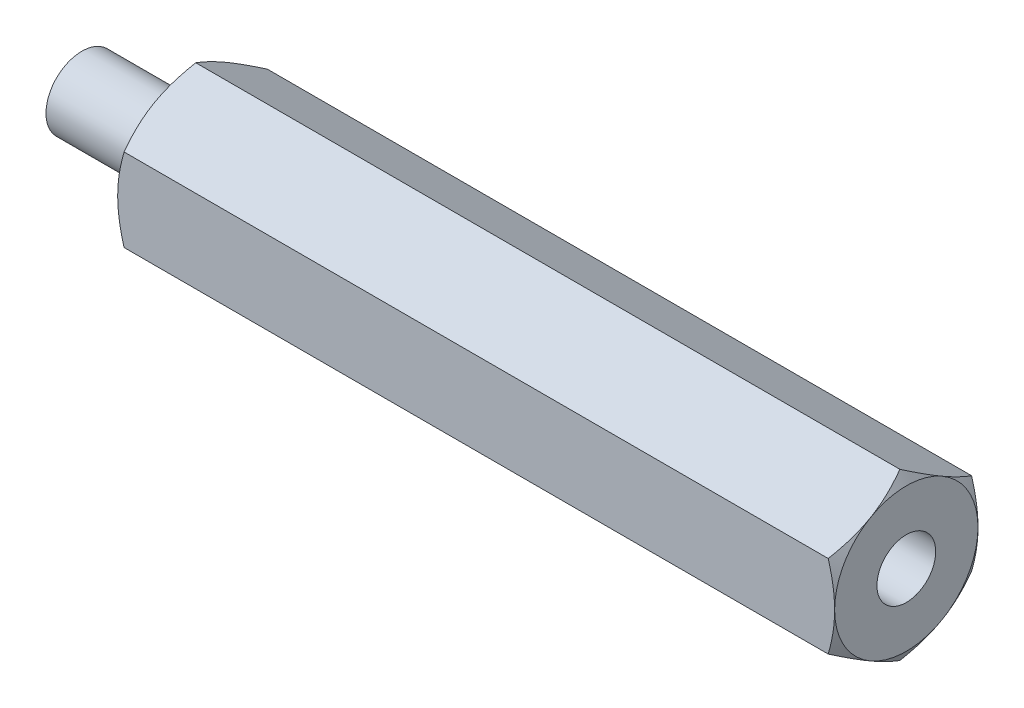
SolidWorks part; units mm, degrees
material "一般構造用鋼またはSUM材"
ref_plane "Front Plane" through (0, 0, 0) normal (0, 0, 1) x (1, 0, 0)
ref_plane "Top Plane" through (0, 0, 0) normal (0, 1, 0) x (1, 0, 0)
ref_plane "Right Plane" through (0, 0, 0) normal (1, 0, 0) x (0, 0, -1)
ref_axis "Axis_X" through (-88.99, 0, 0) along (1, 0, 0)
ref_axis "Axis_Y" through (0, 55, 0) along (0, -1, 0)
ref_axis "Axis_Z" through (0, 0, -88.99) along (0, 0, 1)
sketch "Sketch1" plane through (0, 0, 0) normal (1, 0, 0) x (0, 0, -1)
  line L1 (3, 1.7321) -> (0, 3.4641)
  line L2 (0, 3.4641) -> (-3, 1.7321)
  line L3 (-3, 1.7321) -> (-3, -1.7321)
  line L4 (-3, -1.7321) -> (0, -3.4641)
  line L5 (0, -3.4641) -> (3, -1.7321)
  line L6 (3, -1.7321) -> (3, 1.7321)
  circle A0 centre (0, 0) radius 3 construction
  dimension "B" = 6
extrude "Boss-Extrude1" add sketch "Sketch1" along normal blind 30
sketch "Sketch2" plane through (0, 0, 0) normal (0, 0, 1) x (1, 0, 0)
  line L0 (0, 3.4641) -> (0.2679, 3.4641)
  line L1 (0, 3.4641) -> (0, 3)
  line L2 (0.2679, 3.4641) -> (0, 3)
  line L3 (29.7321, 3.4641) -> (30, 3)
  line L4 (30, 3.4641) -> (30, 3)
  line L5 (30, 3.4641) -> (29.7321, 3.4641)
  line L6 (30, 3.4641) -> (0, 3.4641) construction
  line L12 (30, 3.4641) -> (30, 1.7321) construction
  line L13 (0, 0) -> (30, 0) construction
  dimension "FIX_1" = 30
revolve "Cut-Revolve1" cut sketch "Sketch2" angle 360 about axis through (-88.99, 0, 0) along (1, 0, 0)
hole_wizard "Tap1" positions "Sketch3" profile "Sketch4" hole size "M3x0.5" standard "JIS"
sketch "Sketch3" plane through (30, -0.0864, -2.1297) normal (1, 0, 0) x (0, 0, -1)
  point P0 (-2.1297, 0.0864)
sketch "Sketch4" plane through (30, 0, 0) normal (0, 1, 0) x (0, 0, -1)
  line L0 (0, 0) -> (0, 9.2388)
  line L1 (0, 9.2388) -> (1.2295, 8.5)
  line L2 (1.2295, 8.5) -> (1.2295, 0)
  line L5 (1.2295, 0) -> (0, 0)
  line L10 (0, 9.2388) -> (-1.2295, 8.5) construction
  line L11 (0, -6.35) -> (0, 107.95) construction
  dimension "HSD_1" = 2.459
  dimension "HSL_1" = 8.5
  dimension "FIX_5" = 118
cosmetic thread "Thread1" parameters "KSS_1"=6, "M"=3
sketch "Sketch5" plane through (0, 0, 0) normal (0, 0, 1) x (1, 0, 0)
  line L0 (0, 1.15) -> (-1, 1.15)
  line L1 (0, 1.7321) -> (0, -1.7321) construction
  line L2 (-1, 1.15) -> (-1, 1.5)
  line L3 (-1, 1.5) -> (-4.5, 1.5)
  line L4 (-4.5, 1.5) -> (-4.5, 0)
  line L5 (-4.5, 0) -> (0, 0)
  line L6 (0, -3) -> (0, 3) construction
  line L7 (0, 0) -> (0, 1.15)
  line L8 (0, 0) -> (-4.5, 0) construction
  dimension "M" = 3
  dimension "G_s" = 1
  dimension "MC" = 2.3
  dimension "KSS_2" = 4.5
revolve "Revolve1" add sketch "Sketch5" angle 360 about axis through (-88.99, 0, 0) along (1, 0, 0)
cosmetic thread "Thread2" parameters "KSS_3"=3.5
equation "\"KSS_1@Thread1\" = \"M@Thread1\" * 2"
equation "\"KSS_2@Sketch5\" = \"M@Sketch5\" * 1.5"
equation "\"KSS_3@Thread2\" = \"KSS_2@Sketch5\" - \"G_s@Sketch5\""
